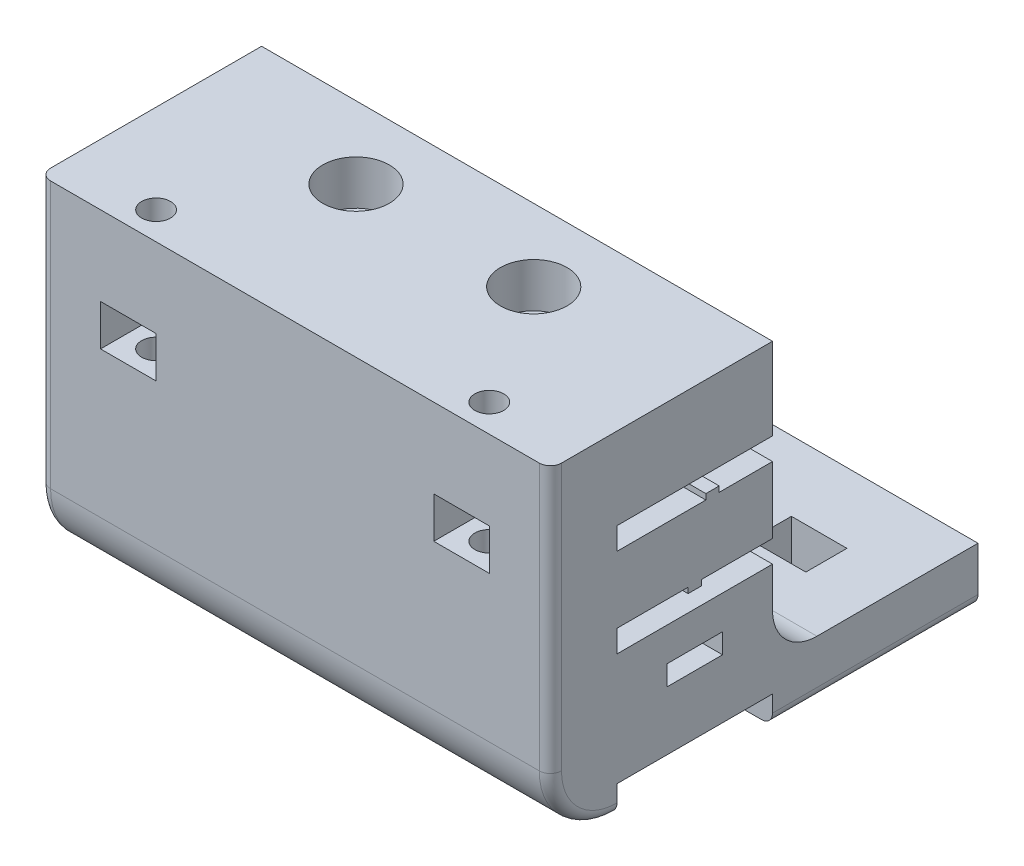
SolidWorks part; units mm, degrees
material "1060 Сплав"
ref_plane "Front" through (0, 0, 0) normal (0, 0, 1) x (1, 0, 0)
ref_plane "Top" through (0, 0, 0) normal (0, 1, 0) x (1, 0, 0)
ref_plane "Right" through (0, 0, 0) normal (1, 0, 0) x (0, 0, -1)
sketch "Эскиз1" plane through (0, 0, 0) normal (0, 0, 1) x (1, 0, 0)
  line L1 (-23, -15) -> (23, -15)
  line L2 (-23, -15) -> (-23, 15)
  line L3 (-23, 15) -> (23, 15)
  line L4 (23, -15) -> (23, 15)
  line L5 (-23, -15) -> (23, 15) construction
  line L6 (-23, 15) -> (23, -15) construction
  point P0 (0, 0)
  dimension "D1" = 30
  dimension "D2" = 46
extrude "Бобышка-Вытянуть1" add sketch "Эскиз1" along normal blind 5
sketch "Эскиз2" plane through (0, 0, 0) normal (0, 0, -1) x (-1, 0, 0)
  line L0 (23, 15) -> (23, -15) construction
  line L1 (-23, -15) -> (23, -15)
  line L2 (-23, -15) -> (-23, -10)
  line L3 (-23, -10) -> (23, -10)
  line L4 (23, -15) -> (23, -10)
  dimension "D1" = 5
extrude "Бобышка-Вытянуть2" add sketch "Эскиз2" along normal blind 33.5
sketch "Эскиз4" plane through (0, 15, 0) normal (0, 1, 0) x (1, 0, 0)
  line L0 (23, -2.5) -> (-23, -2.5) construction
  line L1 (23, -5) -> (23, 0) construction
  line L2 (-23, -5) -> (-23, 0) construction
  circle A0 centre (15, -2.5) radius 1.3
  circle A1 centre (-15, -2.5) radius 1.3
  point P10 (0, -2.5)
  dimension "D1" = 15
  dimension "D2" = 15
extrude "Вырез-Вытянуть2" cut sketch "Эскиз4" against normal blind 15
sketch "Эскиз5" plane through (0, 0, -33.5) normal (0, 0, -1) x (-1, 0, 0)
  line L0 (-23, -12.5) -> (23, -12.5) construction
  line L1 (-23, -10) -> (-23, -15) construction
  line L2 (23, -15) -> (23, -10) construction
  circle A0 centre (-20, -12.5) radius 1.3
  circle A1 centre (20, -12.5) radius 1.3
  point P10 (0, -12.5)
  dimension "D1" = 20
  dimension "D2" = 20
extrude "Вырез-Вытянуть3" cut sketch "Эскиз5" against normal blind 15
sketch "Эскиз6" plane through (0, -10, 0) normal (0, 1, 0) x (1, 0, 0)
  line L0 (-23, 23.5) -> (23, 23.5) construction
  line L1 (-23, 33.5) -> (-23, 0) construction
  line L2 (23, 33.5) -> (23, 0) construction
  line L3 (-23, 33.5) -> (23, 33.5) construction
  line L5 (-17.5, 23.5) -> (-12.5, 23.5)
  line L6 (-17.5, 23.5) -> (-17.5, 27.2)
  line L7 (-17.5, 27.2) -> (-12.5, 27.2)
  line L8 (-12.5, 23.5) -> (-12.5, 27.2)
  line L9 (12.5, 23.5) -> (17.5, 23.5)
  line L10 (12.5, 23.5) -> (12.5, 27.2)
  line L11 (12.5, 27.2) -> (17.5, 27.2)
  line L12 (17.5, 23.5) -> (17.5, 27.2)
  point P16 (0, 23.5)
  dimension "D1" = 10
  dimension "D2" = 3.7
  dimension "D3" = 5
  dimension "D4" = 3.7
  dimension "D5" = 5
  dimension "D6" = 12.5
  dimension "D7" = 12.5
extrude "Вырез-Вытянуть4" cut sketch "Эскиз6" against normal up to next
sketch "Эскиз7" plane through (0, 0, 0) normal (0, 0, -1) x (-1, 0, 0)
  line L1 (23, 15) -> (-23, 15)
  line L2 (23, 15) -> (23, -10)
  line L3 (23, -10) -> (-23, -10)
  line L4 (-23, 15) -> (-23, -10)
extrude "Бобышка-Вытянуть3" add sketch "Эскиз7" along normal blind 15
sketch "Эскиз8" plane through (0, 0, -15) normal (0, 0, -1) x (-1, 0, 0)
  line L0 (-23, 7.62) -> (23, 7.62)
  line L1 (23, -10) -> (23, 15) construction
  line L2 (-23, 15) -> (-23, -10) construction
  line L3 (-23, 5.62) -> (-23, 7.62)
  line L5 (23, 5.62) -> (-23, 5.62)
  line L6 (-23, -2.38) -> (-23, -0.38)
  line L7 (23, 5.62) -> (23, 7.62)
  line L8 (23, -2.38) -> (-23, -2.38)
  line L9 (23, -2.38) -> (23, -0.38)
  line L10 (-23, -0.38) -> (23, -0.38)
  dimension "D2" = 2
extrude "Вырез-Вытянуть5" cut sketch "Эскиз8" against normal blind 14
sketch "Эскиз10" plane through (0, 0, 5) normal (0, 0, 1) x (1, 0, 0)
  line L0 (0, 15) -> (0, -15) construction
  line L1 (23, 15) -> (-23, 15) construction
  line L2 (-23, -15) -> (23, -15) construction
  line L3 (0, 6) -> (15, 6) construction
  line L4 (-17.5, 7.85) -> (-12.5, 4.15) construction
  line L5 (17.5, 4.15) -> (12.5, 4.15)
  line L6 (17.5, 4.15) -> (17.5, 7.85)
  line L7 (17.5, 7.85) -> (12.5, 7.85)
  line L8 (12.5, 4.15) -> (12.5, 7.85)
  line L9 (17.5, 4.15) -> (12.5, 7.85) construction
  line L10 (17.5, 7.85) -> (12.5, 4.15) construction
  line L11 (-17.5, 4.15) -> (-12.5, 7.85) construction
  line L12 (-12.5, 4.15) -> (-12.5, 7.85)
  line L13 (-17.5, 7.85) -> (-12.5, 7.85)
  line L14 (-17.5, 4.15) -> (-17.5, 7.85)
  line L15 (-17.5, 4.15) -> (-12.5, 4.15)
  dimension "D1" = 15
  dimension "D2" = 5
  dimension "D3" = 3.7
  dimension "D4" = 9
extrude "Вырез-Вытянуть7" cut sketch "Эскиз10" against normal blind 5
fillet "Скругление1" radius 6 1 edges at (0, -15, 5)
fillet "Скругление2" radius 4 1 edges at (0, -10, -15)
sketch "Эскиз11" plane through (0, 0, -15) normal (0, 0, -1) x (-1, 0, 0)
  line L0 (-23, 5.62) -> (23, 5.62) construction
  line L1 (-2.5, 5.62) -> (2.5, 5.62)
  line L2 (-2.5, 5.62) -> (-2.5, -17.5157)
  line L3 (-2.5, -17.5157) -> (2.5, -17.5157)
  line L4 (2.5, 5.62) -> (2.5, -17.5157)
  line L5 (-23, 5.62) -> (23, 5.62) construction
  point P0 (0, 5.62)
  dimension "D1" = 2.5
  dimension "D2" = 2.5
extrude "Вырез-Вытянуть8" cut sketch "Эскиз11" against normal blind 14
fillet "Скругление3" radius 4 4 edges at (-2.5, -2.38, -8) (-2.5, 5.62, -8) (2.5, 5.62, -8) (2.5, -2.38, -8)
fillet "Скругление4" radius 1 6 edges at (23, -15, -17.25) (23, -13.2426, 3.2426) (-23, -15, -17.25) (-23, -13.2426, 3.2426) (23, 3, 5) (-23, 3, 5)
sketch "Эскиз12" plane through (23, 0, 0) normal (1, 0, 0) x (0, 0, -1)
  line L0 (1, 5.62) -> (9, 5.62) construction
  line L1 (1, 5.62) -> (15, 5.62) construction
  line L2 (15, 5.62) -> (10.2, 5.62) construction
  line L3 (1, -0.38) -> (15, -0.38) construction
  line L4 (9, 6.12) -> (10.2, 6.12)
  line L5 (9, 6.12) -> (9, 5.62)
  line L6 (7.4, -0.88) -> (8.6, -0.88)
  line L7 (10.2, 6.12) -> (10.2, 5.62)
  line L8 (9, 5.62) -> (10.2, 5.62)
  line L9 (8.6, -0.38) -> (7.4, -0.38)
  line L10 (7.4, -0.38) -> (7.4, -0.88)
  line L11 (8.6, -0.38) -> (8.6, -0.88)
  line L12 (15, 5.62) -> (15, -0.38) construction
  point P19 (8.6, -0.63)
  dimension "D1" = 4.8
  dimension "D2" = 1.2
  dimension "D3" = 0.5
  dimension "D4" = 0.5
  dimension "D5" = 6.4
extrude "Бобышка-Вытянуть4" add sketch "Эскиз12" against normal blind 10
sketch "Эскиз13" plane through (-23, 0, 0) normal (-1, 0, 0) x (0, 0, 1)
  line L0 (-8.6, 5.62) -> (-7.4, 5.62)
  line L1 (-8.6, 6.12) -> (-7.4, 6.12)
  line L2 (-8.6, 6.12) -> (-8.6, 5.62)
  line L3 (-10.2, -0.88) -> (-9, -0.88)
  line L4 (-7.4, 6.12) -> (-7.4, 5.62)
  line L6 (-10.2, -0.38) -> (-9, -0.38)
  line L8 (-10.2, -0.38) -> (-10.2, -0.88)
  line L9 (-9, -0.38) -> (-9, -0.88)
  line L11 (-15, -0.38) -> (-15, 5.62) construction
  dimension "D1" = 1.2
  dimension "D2" = 4.8
  dimension "D3" = 1.2
extrude "Бобышка-Вытянуть5" add sketch "Эскиз13" against normal blind 10
sketch "Эскиз14" plane through (0, -15, 0) normal (0, -1, 0) x (1, 0, 0)
  line L1 (-28.5402, -1) -> (28.5402, -1)
  line L2 (-28.5402, -1) -> (-28.5402, -15)
  line L3 (-28.5402, -15) -> (28.5402, -15)
  line L4 (28.5402, -1) -> (28.5402, -15)
  line L5 (-28.5402, -1) -> (28.5402, -15) construction
  line L6 (-28.5402, -15) -> (28.5402, -1) construction
  point P0 (0, -8)
extrude "Вырез-Вытянуть9" cut sketch "Эскиз14" against normal blind 2.5
fillet "Скругление5" radius 4 2 edges at (2.5, -12.5, -8) (-2.5, -12.5, -8)
sketch "Эскиз15" plane through (0, -12.5, 0) normal (0, -1, 0) x (1, 0, 0)
  line L0 (-23, -8) -> (23, -8) construction
  line L1 (-23, -1) -> (-23, -15) construction
  line L2 (23, -15) -> (23, -1) construction
  circle A2 centre (-19, -8) radius 1.3
  circle A3 centre (19, -8) radius 1.3
  dimension "D1" = 4
  dimension "D2" = 4
extrude "Вырез-Вытянуть10" cut sketch "Эскиз15" against normal blind 8
sketch "Эскиз16" plane through (-23, 0, 0) normal (-1, 0, 0) x (0, 0, 1)
  line L0 (-8, -12.5) -> (-8, -6.3) construction
  line L1 (-10.5, -5.4) -> (-5.5, -5.4)
  line L2 (-10.5, -5.4) -> (-10.5, -7.2)
  line L3 (-10.5, -7.2) -> (-5.5, -7.2)
  line L4 (-5.5, -5.4) -> (-5.5, -7.2)
  line L5 (-10.5, -5.4) -> (-5.5, -7.2) construction
  line L6 (-10.5, -7.2) -> (-5.5, -5.4) construction
  line L7 (-1, -12.5) -> (-15, -12.5) construction
  point P0 (-8, -6.3)
  dimension "D1" = 5
  dimension "D2" = 1.8
  dimension "D3" = 6.2
extrude "Вырез-Вытянуть11" cut sketch "Эскиз16" against normal blind 7
sketch "Эскиз17" plane through (23, 0, 0) normal (1, 0, 0) x (0, 0, -1)
  line L0 (8, -12.5) -> (8, -6.3) construction
  line L1 (15, -12.5) -> (1, -12.5) construction
  line L3 (5.5, -5.4) -> (10.5, -5.4)
  line L4 (5.5, -5.4) -> (5.5, -7.2)
  line L5 (5.5, -7.2) -> (10.5, -7.2)
  line L6 (10.5, -5.4) -> (10.5, -7.2)
  line L7 (5.5, -5.4) -> (10.5, -7.2) construction
  line L8 (5.5, -7.2) -> (10.5, -5.4) construction
  dimension "D1" = 6.2
  dimension "D2" = 1.8
  dimension "D3" = 5
extrude "Вырез-Вытянуть12" cut sketch "Эскиз17" against normal blind 7
sketch "Эскиз18" plane through (0, 15, 0) normal (0, 1, 0) x (1, 0, 0)
  line L0 (0, 15) -> (0, -5) construction
  line L1 (-23, 15) -> (23, 15) construction
  line L2 (22, -5) -> (-22, -5) construction
  line L3 (0, 8.5) -> (8, 8.5) construction
  circle A0 centre (8, 8.5) radius 3
  circle A1 centre (-8, 8.5) radius 3
  dimension "D2" = 13.5
  dimension "D1" = 8
extrude "Вырез-Вытянуть13" cut sketch "Эскиз18" against normal blind 4
